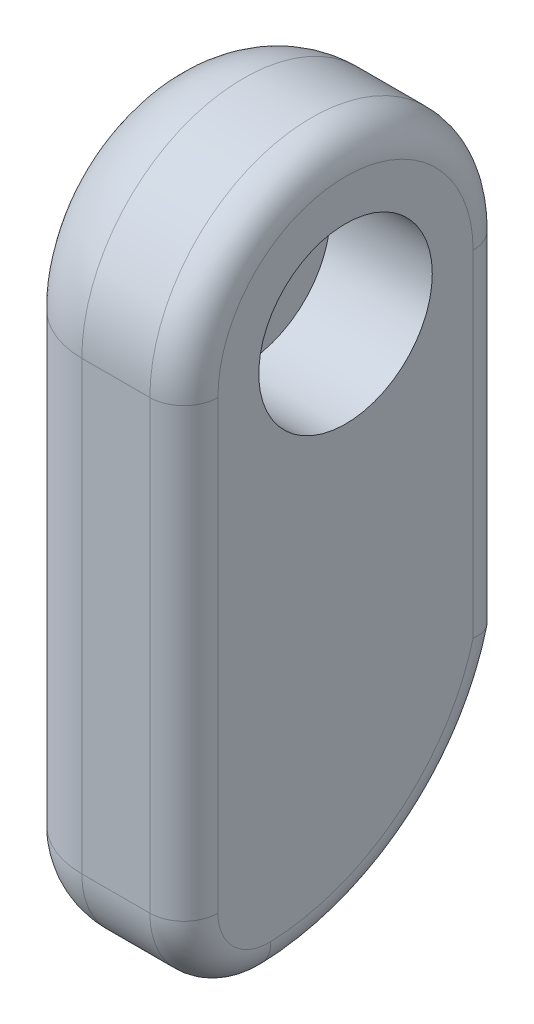
SolidWorks part; units mm, degrees
ref_plane "Plano frontal" through (0, 0, 0) normal (0, 0, 1) x (1, 0, 0)
ref_plane "Plano superior" through (0, 0, 0) normal (0, 1, 0) x (1, 0, 0)
ref_plane "Plano direito" through (0, 0, 0) normal (1, 0, 0) x (0, 0, -1)
sketch "Esboço1" plane through (0, 0, 0) normal (1, 0, 0) x (0, 0, -1)
  line L1 (9.5, 0) -> (9.5, -20)
  line L2 (-9.5, 0) -> (-9.5, -30.5)
  circle A0 centre (0, 0) radius 9.5
  arc A1 (9.5, -20) -> (-9.5, -30.5) centre (-4.8455, -16.482) cw
  dimension "D1" = 19
  dimension "D2" = 30.5
  dimension "D3" = 14.7705
  dimension "D4" = 20
extrude "Ressalto-extrusão1" add sketch "Esboço1" against normal blind 11 contours A0 | A1 L1 A0 L2 region at (0, 0, 0) region at (0, -18.3094, 0.6089)
fillet "Filete1" radius 5 1 edges at (-5.5, -30.5, 9.5)
sketch "Esboço2" plane through (0, 0, 0) normal (1, 0, 0) x (0, 0, -1)
  circle A0 centre (0, 0) radius 5.1
  dimension "D1" = 10.2
extrude "Corte-extrusão1" cut sketch "Esboço2" against normal blind 6
fillet "Filete2" radius 5 5 edges at (-11, -10, -9.5) (-11, 9.5, 0) (-11, -13.1232, 9.5) (-11, -29.8439, 7.9725) (-11, -27.9408, -4.4747)
fillet "Filete4" radius 2 5 edges at (0, -27.9408, -4.4747) (0, -29.8439, 7.9725) (0, -13.1232, 9.5) (0, 9.5, 0) (0, -10, -9.5)
